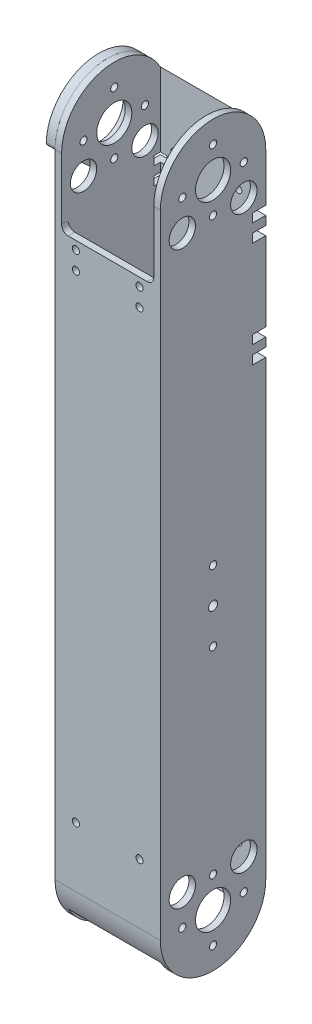
SolidWorks part; units mm, degrees
note: The reader was unsure of these and kept them because the rebuilt part matched: shared geometry of "Sketch1<6>", "Sketch1<7>", "Sketch1<8>".
ref_plane "Front Plane" through (0, 0, 0) normal (0, 0, 1) x (1, 0, 0)
ref_plane "Top Plane" through (0, 0, 0) normal (0, 1, 0) x (1, 0, 0)
ref_plane "Right Plane" through (0, 0, 0) normal (1, 0, 0) x (0, 0, -1)
sketch "Sketch1" plane through (0, 0, 0) normal (1, 0, 0) x (0, 0, -1)
  line L0 (41.3066, 186.9315) -> (41.3066, 644.1315)
  line L1 (3.2066, 186.9315) -> (3.2066, 148.8315) construction
  line L2 (41.3066, 415.5315) -> (-34.8934, 415.5315) construction
  line L3 (3.2066, 644.1315) -> (3.2066, 682.2315) construction
  line L4 (-34.8934, 186.9315) -> (-34.8934, 644.1315)
  line L5 (36.5441, 168.4864) -> (36.5441, 662.5766)
  line L6 (36.5441, 186.9315) -> (36.5441, 644.1315) construction
  line L7 (-30.1309, 168.4864) -> (-30.1309, 662.5766)
  circle A0 centre (3.2066, 186.9315) radius 14.3129 construction
  circle A1 centre (3.2066, 186.9315) radius 14.3129 construction
  arc A2 (-34.8934, 186.9315) -> (41.3066, 186.9315) centre (3.2066, 186.9315) ccw
  circle A3 centre (3.2066, 644.1315) radius 14.3129 construction
  arc A4 (-34.8934, 644.1315) -> (41.3066, 644.1315) centre (3.2066, 644.1315) cw
  circle A5 centre (3.2066, 644.1315) radius 12.7
  circle A6 centre (3.2066, 186.9315) radius 12.7
  dimension "D4" = 25.4
  dimension "D1" = 457.2
  dimension "D2" = 76.2
  dimension "D3" = 4.7625
extrude "Boss-Extrude1" add sketch "Sketch1" against normal blind 4.7625 from surface contours A4 L7 A2 L5 A1 A3 | A4 L4 A2 L7 | A4 L5 A2 L0
extrude "Boss-Extrude2" add sketch "Sketch1<6>" along normal blind 4.7625 from surface separate body contours A4 L7 A2 L5 A1 A3 | A4 L4 A2 L7 | A4 L5 A2 L0
sketch "Sketch1<6>" plane through (0, 0, 0) normal (1, 0, 0) x (0, 0, -1) same geometry as "Sketch1"
extrude "Boss-Extrude3" add sketch "Sketch1<7>" along normal up to surface (33.3375 mm away) contours A4 L4 A2 L7 | A4 L5 A2 L0
sketch "Sketch1<7>" plane through (0, 0, 0) normal (1, 0, 0) x (0, 0, -1) same geometry as "Sketch1"
extrude "Boss-Extrude4" add sketch "Sketch1<8>" against normal up to surface (38.1 mm away) contours A4 L4 A2 L7 | A4 L5 A2 L0
sketch "Sketch1<8>" plane through (0, 0, 0) normal (1, 0, 0) x (0, 0, -1) same geometry as "Sketch1"
sketch "Sketch2" plane through (0, 0, 34.8934) normal (0, 0, 1) x (1, 0, 0)
  line L0 (29, 594.769) -> (-29, 594.769) construction
  line L1 (33.3375, 594.769) -> (-33.3375, 594.769)
  line L2 (-33.3375, 168.4864) -> (-33.3375, 662.5766) construction
  line L3 (-33.3375, 594.769) -> (-33.3375, 662.5766)
  line L4 (33.3375, 662.5766) -> (33.3375, 168.4864) construction
  line L5 (33.3375, 662.5766) -> (33.3375, 594.769)
  line L6 (0, 594.769) -> (0, 662.5766) construction
  line L7 (-33.3375, 662.5766) -> (33.3375, 662.5766)
  line L8 (-33.3375, 662.5766) -> (33.3375, 662.5766) construction
  line L9 (-33.3375, 662.5766) -> (33.3375, 662.5766) construction
extrude "Cut-Extrude1" cut sketch "Sketch2" against normal up to surface (4.7625 mm away) up to face at (0, 415.5315, 30.1309)
sketch "Sketch3" plane through (0, 0, 34.8934) normal (0, 0, 1) x (1, 0, 0)
  circle A0 centre (23, 588.769) radius 3.3 construction
  circle A1 centre (23, 575.769) radius 3.3 construction
  circle A2 centre (-23, 588.769) radius 3.3 construction
  circle A3 centre (-23, 575.769) radius 3.3 construction
  circle A4 centre (23, 230.269) radius 3.3 construction
  circle A5 centre (-23, 230.269) radius 3.3 construction
  circle A6 centre (23, 588.769) radius 3.3 construction
  circle A7 centre (23, 575.769) radius 3.3 construction
  circle A8 centre (-23, 588.769) radius 3.3 construction
  circle A9 centre (-23, 575.769) radius 3.3 construction
  circle A10 centre (23, 230.269) radius 3.3 construction
  circle A11 centre (-23, 230.269) radius 3.3 construction
  circle A12 centre (23, 575.769) radius 2.6035
  circle A13 centre (23, 588.769) radius 2.6035
  circle A14 centre (-23, 575.769) radius 2.6035
  circle A15 centre (-23, 588.769) radius 2.6035
  circle A16 centre (-23, 230.269) radius 2.6035
  circle A17 centre (23, 230.269) radius 2.6035
  dimension "D1" = 5.207
extrude "Cut-Extrude2" cut sketch "Sketch3" against normal up to surface (4.7625 mm away) up to face at (0, 381.6277, 30.1309)
sketch "Sketch4" plane through (0, 0, -41.3066) normal (0, 0, -1) x (-1, 0, 0)
  circle A0 centre (23, 614.1315) radius 3.3 construction
  circle A1 centre (-23, 614.1315) radius 3.3 construction
  circle A2 centre (-23, 205.6315) radius 3.3 construction
  circle A3 centre (-23, 218.6315) radius 3.3 construction
  circle A4 centre (23, 218.6315) radius 3.3 construction
  circle A5 centre (23, 205.6315) radius 3.3 construction
  circle A6 centre (23, 614.1315) radius 3.3 construction
  circle A7 centre (-23, 614.1315) radius 3.3 construction
  circle A8 centre (-23, 205.6315) radius 3.3 construction
  circle A9 centre (-23, 218.6315) radius 3.3 construction
  circle A10 centre (23, 218.6315) radius 3.3 construction
  circle A11 centre (23, 205.6315) radius 3.3 construction
  circle A12 centre (-23, 205.6315) radius 2.6035
  circle A13 centre (-23, 218.6315) radius 2.6035
  circle A14 centre (23, 218.6315) radius 2.6035
  circle A15 centre (23, 205.6315) radius 2.6035
  circle A16 centre (23, 614.1315) radius 2.6035
  circle A17 centre (-23, 614.1315) radius 2.6035
  dimension "D1" = 5.207
extrude "Cut-Extrude3" cut sketch "Sketch4" against normal up to surface (4.7625 mm away) up to face at (0, 415.5315, -36.5441)
sketch "Sketch5" plane through (-38.1, 0, 0) normal (-1, 0, 0) x (0, 0, 1)
  line L0 (-3.2066, 186.9315) -> (-3.2066, 644.1315) construction
  line L1 (-3.2066, 377.4315) -> (34.8934, 377.4315) construction
  line L2 (34.8934, 186.9315) -> (34.8934, 644.1315) construction
  circle A0 centre (-3.2066, 352.0315) radius 2.6035
  circle A1 centre (-3.2066, 402.8315) radius 2.6035
  circle A4 centre (-3.2066, 377.4315) radius 3.2639
  circle A5 centre (-3.2066, 186.9315) radius 12.7 construction
  circle A6 centre (-3.2066, 644.1315) radius 12.7 construction
  circle A7 centre (-3.2066, 186.9315) radius 12.7 construction
  circle A8 centre (-3.2066, 644.1315) radius 12.7 construction
  dimension "D2" = 6.5278
  dimension "D3" = 5.207
  dimension "D1" = 190.5
  dimension "D4" = 25.4
extrude "Cut-Extrude4" cut sketch "Sketch5" against normal through all
sketch "Sketch6" plane through (0, 0, 0) normal (1, 0, 0) x (0, 0, -1)
  circle A0 centre (25.4316, 186.9315) radius 2.6035
  circle A1 centre (3.2066, 666.3565) radius 2.6035
  circle A2 centre (3.2066, 666.3565) radius 2.6035 construction
  circle A3 centre (3.2066, 621.9065) radius 2.6035
  circle A4 centre (3.2066, 621.9065) radius 2.6035 construction
  circle A5 centre (-19.0184, 644.1315) radius 2.6035
  circle A6 centre (-19.0184, 644.1315) radius 2.6035 construction
  circle A7 centre (25.4316, 644.1315) radius 2.6035
  circle A8 centre (25.4316, 644.1315) radius 2.6035 construction
  circle A9 centre (3.2066, 209.1565) radius 2.6035
  circle A10 centre (3.2066, 209.1565) radius 2.6035 construction
  circle A11 centre (3.2066, 164.7065) radius 2.6035
  circle A12 centre (3.2066, 164.7065) radius 2.6035 construction
  circle A13 centre (-19.0184, 186.9315) radius 2.6035
  circle A14 centre (-19.0184, 186.9315) radius 2.6035 construction
  circle A15 centre (25.4316, 186.9315) radius 2.6035
  circle A16 centre (25.4316, 186.9315) radius 2.6035 construction
  circle A17 centre (3.2066, 209.1565) radius 2.6035
  circle A18 centre (-19.0184, 186.9315) radius 2.6035
  circle A19 centre (3.2066, 164.7065) radius 2.6035
  circle A20 centre (-19.0184, 644.1315) radius 2.6035
  circle A21 centre (3.2066, 666.3565) radius 2.6035
  circle A22 centre (25.4316, 644.1315) radius 2.6035
  circle A23 centre (3.2066, 621.9065) radius 2.6035
  dimension "D9" = 5.207
  dimension "D1" = 0
  dimension "D2" = 0
  dimension "D3" = 0
  dimension "D4" = 0
  dimension "D5" = 0
  dimension "D6" = 0
  dimension "D7" = 0
  dimension "D8" = 0
extrude "Cut-Extrude5" cut sketch "Sketch6" against normal through all both and the other way through all
sketch "Sketch7" plane through (38.1, 0, 0) normal (1, 0, 0) x (0, 0, -1)
  line L0 (3.2066, 209.1565) -> (25.4316, 209.1565) construction
  line L1 (-34.8934, 415.5315) -> (41.3066, 415.5315) construction
  line L2 (-19.0184, 186.9315) -> (25.4316, 186.9315) construction
  line L3 (41.3066, 186.9315) -> (41.3066, 644.1315)
  line L4 (-34.8934, 644.1315) -> (-34.8934, 186.9315)
  line L5 (41.3066, 186.9315) -> (41.3066, 644.1315) construction
  line L6 (-34.8934, 644.1315) -> (-34.8934, 186.9315) construction
  line L7 (3.2066, 186.9315) -> (3.2066, 209.1565) construction
  line L8 (25.4316, 186.9315) -> (25.4316, 209.1565) construction
  circle A0 centre (25.4316, 209.1565) radius 9.525
  circle A1 centre (3.2066, 186.9315) radius 12.7 construction
  circle A2 centre (3.2066, 186.9315) radius 12.7 construction
  circle A3 centre (25.4316, 621.9065) radius 9.525
  circle A4 centre (-19.0184, 209.1565) radius 9.525
  arc A5 (41.3066, 644.1315) -> (-34.8934, 644.1315) centre (3.2066, 644.1315) ccw
  arc A6 (-34.8934, 186.9315) -> (41.3066, 186.9315) centre (3.2066, 186.9315) ccw
  arc A7 (41.3066, 644.1315) -> (-34.8934, 644.1315) centre (3.2066, 644.1315) ccw construction
  circle A8 centre (-19.0184, 621.9065) radius 9.525
  arc A15 (-18.3823, 194.8435) -> (-18.3823, 179.0196) centre (-19.0184, 186.9315) ccw
  arc A24 (-34.8934, 186.9315) -> (41.3066, 186.9315) centre (3.2066, 186.9315) ccw construction
  arc A25 (-18.3823, 194.8435) -> (-4.7054, 208.5204) centre (-17.3645, 207.5026) ccw
  arc A26 (11.1185, 208.5204) -> (-4.7054, 208.5204) centre (3.2066, 209.1565) ccw
  arc A27 (11.1185, 208.5204) -> (24.7955, 194.8435) centre (23.7777, 207.5026) ccw
  arc A28 (24.7955, 179.0196) -> (24.7955, 194.8435) centre (25.4316, 186.9315) ccw
  arc A29 (24.7955, 179.0196) -> (11.1185, 165.3426) centre (23.7777, 166.3604) ccw
  arc A30 (-4.7054, 165.3426) -> (11.1185, 165.3426) centre (3.2066, 164.7065) ccw
  arc A31 (-4.7054, 165.3426) -> (-18.3823, 179.0196) centre (-17.3645, 166.3604) ccw
  arc A32 (-18.3823, 194.8435) -> (-18.3823, 179.0196) centre (-19.0184, 186.9315) ccw construction
  arc A33 (-18.3823, 194.8435) -> (-4.7054, 208.5204) centre (-17.3645, 207.5026) ccw construction
  arc A34 (11.1185, 208.5204) -> (-4.7054, 208.5204) centre (3.2066, 209.1565) ccw construction
  arc A35 (11.1185, 208.5204) -> (24.7955, 194.8435) centre (23.7777, 207.5026) ccw construction
  arc A36 (24.7955, 179.0196) -> (24.7955, 194.8435) centre (25.4316, 186.9315) ccw construction
  arc A37 (24.7955, 179.0196) -> (11.1185, 165.3426) centre (23.7777, 166.3604) ccw construction
  arc A38 (-4.7054, 165.3426) -> (11.1185, 165.3426) centre (3.2066, 164.7065) ccw construction
  arc A39 (-4.7054, 165.3426) -> (-18.3823, 179.0196) centre (-17.3645, 166.3604) ccw construction
  point P15 (15.9066, 209.1565)
  point P18 (11.1441, 209.1565)
  dimension "D2" = 19.05
  dimension "D1" = 0
  dimension "D4" = 0
extrude "Cut-Extrude6" cut sketch "Sketch7" against normal through all
fillet "Fillet1" radius 4.7625 2 edges at (-33.3375, 594.769, 32.5122) (33.3375, 594.769, 32.5122)
sketch "Sketch8" plane through (-38.1, 0, 0) normal (-1, 0, 0) x (0, 0, 1)
  line L0 (-41.3066, 599.6815) -> (-31.7816, 599.6815) construction
  line L1 (-41.3066, 609.2065) -> (-31.7816, 609.2065)
  line L2 (-41.3066, 644.1315) -> (-41.3066, 186.9315)
  line L3 (34.8934, 186.9315) -> (34.8934, 644.1315)
  line L4 (-41.3066, 644.1315) -> (-41.3066, 186.9315) construction
  line L5 (34.8934, 186.9315) -> (34.8934, 644.1315) construction
  line L6 (-41.3066, 609.2065) -> (-41.3066, 602.8565)
  line L7 (-41.3066, 602.8565) -> (-31.7816, 602.8565)
  line L8 (-31.7816, 609.2065) -> (-31.7816, 602.8565)
  line L9 (-41.3066, 596.5065) -> (-31.7816, 596.5065)
  line L10 (-31.7816, 590.1565) -> (-31.7816, 596.5065)
  line L11 (-41.3066, 590.1565) -> (-31.7816, 590.1565)
  line L12 (-41.3066, 590.1565) -> (-41.3066, 596.5065)
  line L13 (-41.3066, 561.5815) -> (-31.7816, 561.5815) construction
  line L14 (-41.3066, 533.0065) -> (-41.3066, 526.6565)
  line L15 (-41.3066, 533.0065) -> (-31.7816, 533.0065)
  line L16 (-31.7816, 533.0065) -> (-31.7816, 526.6565)
  line L17 (-41.3066, 526.6565) -> (-31.7816, 526.6565)
  line L18 (-41.3066, 520.3065) -> (-31.7816, 520.3065)
  line L19 (-31.7816, 513.9565) -> (-31.7816, 520.3065)
  line L20 (-41.3066, 513.9565) -> (-31.7816, 513.9565)
  line L21 (-41.3066, 513.9565) -> (-41.3066, 520.3065)
  arc A2 (-41.3066, 186.9315) -> (34.8934, 186.9315) centre (-3.2066, 186.9315) ccw
  arc A3 (34.8934, 644.1315) -> (-41.3066, 644.1315) centre (-3.2066, 644.1315) ccw
  arc A4 (-41.3066, 186.9315) -> (34.8934, 186.9315) centre (-3.2066, 186.9315) ccw construction
  arc A5 (34.8934, 644.1315) -> (-41.3066, 644.1315) centre (-3.2066, 644.1315) ccw construction
  point P12 (-41.3066, 593.3315)
  point P17 (-41.3066, 606.0315)
  point P29 (-41.3066, 529.8315)
  dimension "D2" = 38.1
  dimension "D3" = 12.7
  dimension "D4" = 9.525
  dimension "D5" = 6.35
  dimension "D6" = 63.5
  dimension "D1" = 0
extrude "Cut-Extrude7" cut sketch "Sketch8" against normal blind 9.525
mirror "Mirror1" about plane through (0, 0, 0) normal (1, 0, 0) of "Cut-Extrude7"
sketch "Sketch9" plane through (-38.1, 0, 0) normal (-1, 0, 0) x (0, 0, 1)
  line L0 (-41.3066, 644.1315) -> (-3.2066, 609.2065)
  line L1 (-3.2066, 609.2065) -> (-3.2066, 644.1315) construction
  line L2 (34.8934, 644.1315) -> (-3.2066, 609.2065)
  line L3 (-31.7816, 644.1315) -> (-38.1316, 644.1315)
  line L4 (25.3684, 644.1315) -> (31.7184, 644.1315)
  line L5 (-3.2066, 672.7065) -> (-3.2066, 679.0565) construction
  line L6 (-0.0316, 672.5296) -> (-0.0316, 678.9119)
  line L7 (-6.3816, 672.5296) -> (-6.3816, 678.9119)
  line L8 (-6.3816, 672.7065) -> (-6.3816, 679.0565) construction
  line L9 (-0.0316, 672.7065) -> (-0.0316, 679.0565) construction
  arc A0 (34.8934, 644.1315) -> (-41.3066, 644.1315) centre (-3.2066, 644.1315) ccw construction
  arc A1 (34.8934, 644.1315) -> (-41.3066, 644.1315) centre (-3.2066, 644.1315) ccw
  circle A2 centre (-3.2066, 621.9065) radius 2.6035 construction
  circle A3 centre (19.0184, 644.1315) radius 2.6035 construction
  circle A4 centre (-3.2066, 666.3565) radius 2.6035 construction
  circle A5 centre (-25.4316, 644.1315) radius 2.6035 construction
  circle A6 centre (-3.2066, 621.9065) radius 2.6035
  circle A7 centre (19.0184, 644.1315) radius 2.6035
  circle A8 centre (-3.2066, 666.3565) radius 2.6035
  circle A9 centre (-25.4316, 644.1315) radius 2.6035
  circle A10 centre (-3.2066, 644.1315) radius 17.4625
  arc A11 (31.7184, 644.1315) -> (-38.1316, 644.1315) centre (-3.2066, 644.1315) ccw
  arc A12 (25.3684, 644.1315) -> (-31.7816, 644.1315) centre (-3.2066, 644.1315) ccw
  arc A14 (31.7184, 644.1315) -> (-38.1316, 644.1315) centre (-3.2066, 644.1315) ccw construction
  arc A15 (25.3684, 644.1315) -> (-31.7816, 644.1315) centre (-3.2066, 644.1315) ccw construction
  circle M8 centre (-25.4316, 621.9065) radius 9.525
  circle M9 centre (19.0184, 621.9065) radius 9.525
  circle M12 centre (19.0184, 644.1315) radius 2.6035
  circle M16 centre (-3.2066, 666.3565) radius 2.6035
  circle M17 centre (-25.4316, 644.1315) radius 2.6035
  circle M18 centre (-3.2066, 621.9065) radius 2.6035
  arc M42 (34.8934, 644.1315) -> (-41.3066, 644.1315) centre (-3.2066, 644.1315) ccw
  dimension "D2" = 34.925
  dimension "D1" = 12.7
  dimension "D5" = 90
  dimension "D3" = 3.175
  dimension "D4" = 9.525
  dimension "D6" = 3.175
  dimension "D7" = 3.175
extrude "Boss-Extrude5" add sketch "Sketch9" along normal blind 6.35 separate body contours L2 L0 A10 L4 A12 L3 A11 M42 M8 M9 M17 M18 M16 M12 | A12 L6 A11 L7 | L0 M8 | L2 M9
fillet "Fillet2" radius 2.54 11 edges at (-41.275, 644.1315, 34.8934) (-41.275, 644.1315, -41.3066) (-41.275, 609.2065, -3.2066) (-41.275, 644.1315, 31.7184) (-41.275, 644.1315, 25.3684) (-41.275, 644.1315, -31.7816) (-41.275, 644.1315, -38.1316) (-41.275, 678.9119, -0.0316) (-41.275, 672.5296, -0.0316) (-41.275, 672.5296, -6.3816) (-41.275, 678.9119, -6.3816)
equation "\"BoxThick\"= 3 / 16"
equation "\"D3@Sketch1\"=\"BoxThick\""
equation "\"D1@Boss-Extrude1\"=\"BoxThick\""
equation "\"D1@Boss-Extrude2\"=\"BoxThick\""
equation "\"BoxWidth\"= 3"
equation "\"D2@Sketch1\"=\"BoxWidth\""
